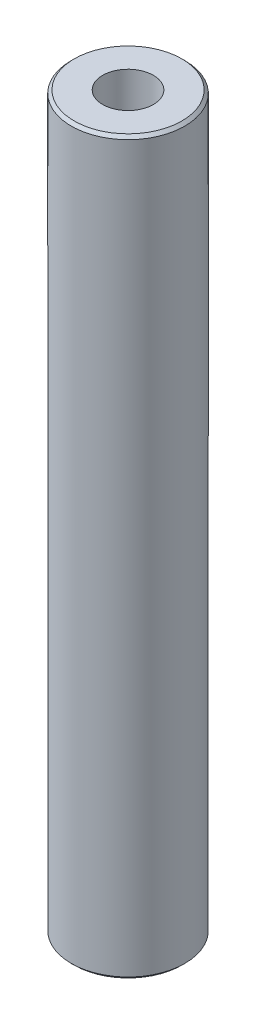
SolidWorks part; units mm, degrees
ref_plane "Front Plane" through (0, 0, 0) normal (0, 0, 1) x (1, 0, 0)
ref_plane "Top Plane" through (0, 0, 0) normal (0, 1, 0) x (1, 0, 0)
ref_plane "Right Plane" through (0, 0, 0) normal (1, 0, 0) x (0, 0, -1)
sketch "Sketch1" plane through (0, 0, 0) normal (0, 1, 0) x (1, 0, 0)
  circle A0 centre (0, 0) radius 17.5
  dimension "SHAFT_OD" = 35
extrude "Boss-Extrude1" add sketch "Sketch1" along normal blind 225.2614
sketch "Sketch2" plane through (0, 0, 0) normal (0, 1, 0) x (1, 0, 0)
  circle A0 centre (0, 0) radius 7.8103
  dimension "BORE_D" = 15.6206
extrude "Cut-Extrude1" cut sketch "Sketch2" along normal through all
chamfer "Chamfer1" distance 0.9142 angle 45 2 edges at (0, 225.2614, 17.5) (0, 0, 17.5)
